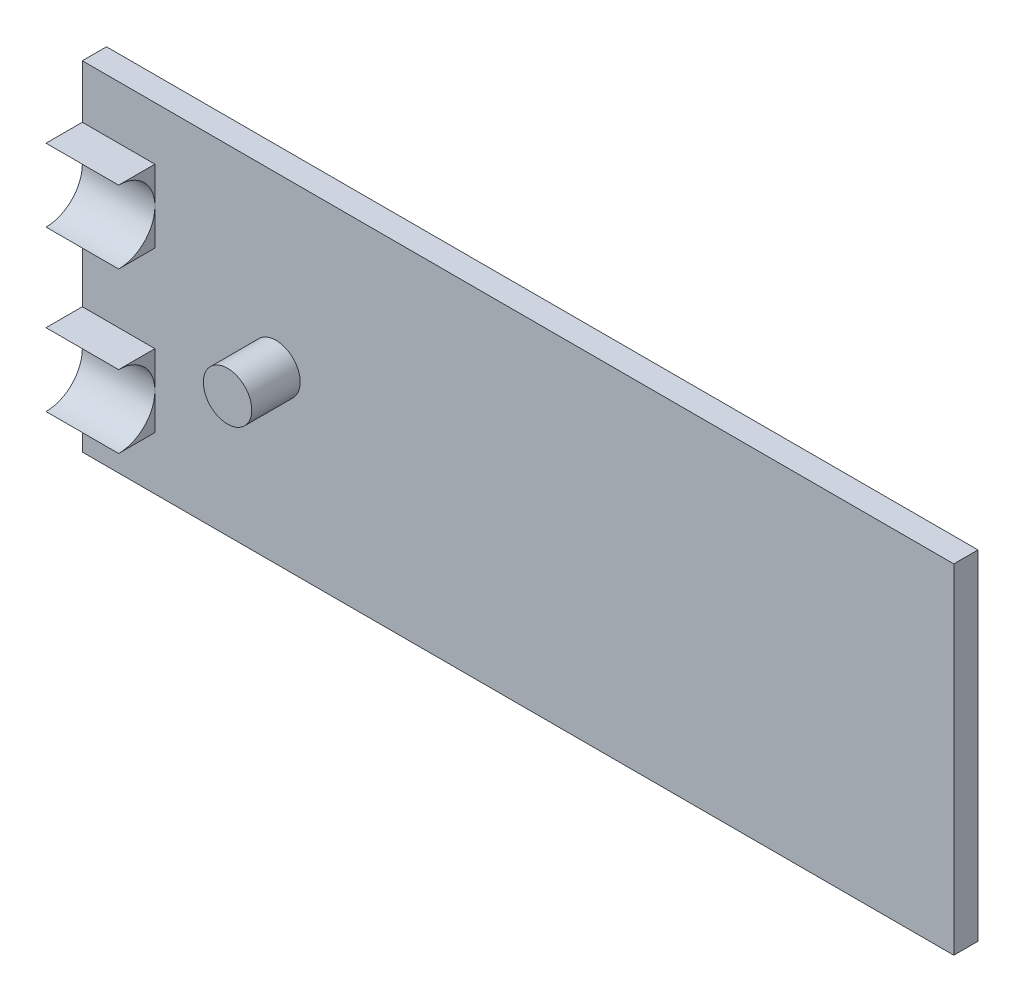
SolidWorks part; units mm, degrees
material "Acrílico (médio-alto impacto)"
ref_plane "Plano frontal" through (0, 0, 0) normal (0, 0, 1) x (1, 0, 0)
ref_plane "Plano superior" through (0, 0, 0) normal (0, 1, 0) x (1, 0, 0)
ref_plane "Plano direito" through (0, 0, 0) normal (1, 0, 0) x (0, 0, -1)
sketch "Esboço1" plane through (0, 0, 0) normal (0, 0, 1) x (1, 0, 0)
  line L1 (-90, -35) -> (90, -35)
  line L2 (-90, -35) -> (-90, 35)
  line L3 (-90, 35) -> (90, 35)
  line L5 (-90, -35) -> (90, 35) construction
  line L6 (-90, 35) -> (90, -35) construction
  line L8 (90, -35) -> (90, 35)
  point P0 (0, 0)
  point P11 (85.3, 0)
  dimension "D1" = 180
  dimension "D2" = 70
extrude "Ressalto-extrusão1" add sketch "Esboço1" along normal blind 5
sketch "Esboço2" plane through (-90, 0, 0) normal (-1, 0, 0) x (0, 0, 1)
  line L0 (12.5, 16.5) -> (12.5, -16.5) construction
  line L1 (12.5, 0) -> (0, 0) construction
  line L2 (0, 35) -> (0, -35) construction
  line L3 (12.5, 24) -> (5, 24)
  line L4 (5, 35) -> (5, -35) construction
  line L5 (12.5, -9) -> (5, -9)
  line L6 (12.5, 9) -> (5, 9)
  line L7 (5, -9) -> (5, -24)
  line L8 (5, -24) -> (12.5, -24)
  line L9 (5, 24) -> (5, 9)
  arc A0 (12.5, 24) -> (12.5, 9) centre (12.5, 16.5) ccw
  arc A1 (12.5, -9) -> (12.5, -24) centre (12.5, -16.5) ccw
  point P3 (12.5, 0)
  line M5 (5, -35) -> (5, 35)
  dimension "D1" = 33
  dimension "D2" = 7.5
  dimension "D3" = 7.5
extrude "Ressalto-extrusão2" add sketch "Esboço2" against normal blind 15 contours A0 L3 L9 | A0 L6 M5 | A1 L5 L7 | A1 L8 M5 | A0 L6 L9 L3 region at (-90, 22.3247, 6.6753) region at (-90, -22.3247, 6.6753) region at (-90, -10.6753, 6.6753) region at (-90, 10.6753, 6.6753)
sketch "Esboço3" plane through (0, 0, 5) normal (0, 0, 1) x (1, 0, 0)
  line L0 (-90, 9) -> (-90, -9) construction
  circle A0 centre (-50, 0) radius 5
  point P2 (-90, 0)
  dimension "D1" = 40
extrude "Ressalto-extrusão3" add sketch "Esboço3" along normal blind 10
